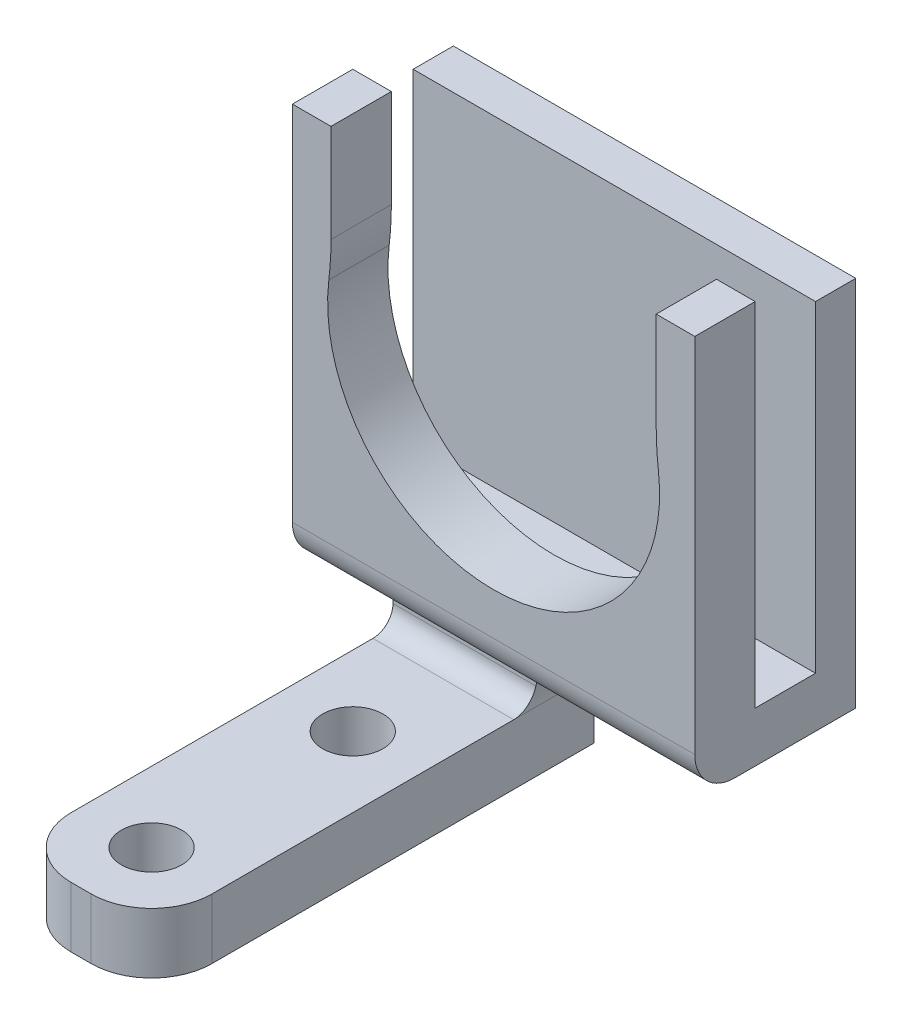
SolidWorks part; units mm, degrees
ref_plane "Front Plane" through (0, 0, 0) normal (0, 0, 1) x (1, 0, 0)
ref_plane "Top Plane" through (0, 0, 0) normal (0, 1, 0) x (1, 0, 0)
ref_plane "Right Plane" through (0, 0, 0) normal (1, 0, 0) x (0, 0, -1)
sketch "Sketch1" plane through (0, 0, 0) normal (0, 0, 1) x (1, 0, 0)
  line L0 (18.0821, 20) -> (20, 20)
  line L1 (0, 0) -> (20, 0)
  line L2 (0, 0) -> (0, 20)
  line L3 (0, 20) -> (1.9179, 20)
  line L4 (20, 0) -> (20, 20)
  line L5 (1.9179, 20) -> (1.9179, 14)
  line L6 (18.0821, 20) -> (18.0821, 14)
  arc A1 (1.9179, 14) -> (18.0821, 14) centre (10, 12.3441) ccw
  dimension "D3" = 6
  dimension "D5" = 8.25
  dimension "D1" = 20
  dimension "D2" = 20
  dimension "D4" = 6
extrude "Boss-Extrude1" add sketch "Sketch1" along normal blind 3 contours L0 L4 L1 L2 L3 L5 A1 L6
sketch "Sketch2" plane through (0, 0, 0) normal (0, 0, -1) x (-1, 0, 0)
  line L0 (0, 0) -> (0, 20) construction
  line L1 (-20, 0) -> (0, 0)
  line L2 (-20, 0) -> (-20, 2.5)
  line L3 (-20, 2.5) -> (0, 2.5)
  line L4 (0, 0) -> (0, 2.5)
  dimension "D1" = 2.5
extrude "Boss-Extrude2" add sketch "Sketch2" along normal blind 5
sketch "Sketch3" plane through (0, 2.5, 0) normal (0, 1, 0) x (1, 0, 0)
  line L0 (0, 5) -> (0, 0) construction
  line L1 (20, 5) -> (0, 5)
  line L2 (20, 5) -> (20, 3)
  line L3 (20, 3) -> (0, 3)
  line L4 (0, 5) -> (0, 3)
  dimension "D1" = 2
extrude "Boss-Extrude3" add sketch "Sketch3" along normal blind 16
fillet "Fillet1" radius 15 2 edges at (18.0821, 14, 1.5) (1.9179, 14, 1.5)
sketch "Sketch4" plane through (0, 0, 0) normal (0, -1, 0) x (1, 0, 0)
  line L1 (7, -5) -> (0, -5)
  line L2 (7, -5) -> (7, 3)
  line L3 (7, 3) -> (0, 3)
  line L4 (0, -5) -> (0, 3)
  dimension "D1" = 7
extrude "Boss-Extrude4" add sketch "Sketch4" along normal blind 5
sketch "Sketch5" plane through (0, 0, -5) normal (0, 0, -1) x (-1, 0, 0)
  line L4 (-7, -8) -> (0, -8)
  line L5 (-7, -5) -> (0, -5)
  line L6 (-7, -5) -> (-7, -8)
  line L7 (-7, -5) -> (-7, 0) construction
  line L9 (0, -5) -> (0, -8)
  line L10 (0, -5) -> (0, 18.5) construction
  dimension "D1" = 3
extrude "Boss-Extrude5" add sketch "Sketch5" against normal blind 22 contours L5 L9 L4 L6
fillet "Fillet2" radius 5 1 edges at (7, 0, -1)
sketch "Sketch6" plane through (0, -8, 0) normal (0, -1, 0) x (-1, 0, 0)
  line L1 (-3.5, -17) -> (-3.5, 5)
  line L2 (-7, 5) -> (0, 5) construction
  line L3 (-7, -17) -> (0, -17) construction
  circle A0 centre (-3.5, -13.5) radius 1.5
  circle A1 centre (-3.5, -3.5) radius 1.5
  point P10 (0, 0)
  point P11 (0, 0)
  dimension "D1" = 3
  dimension "D2" = 3
  dimension "D3" = 3.5
  dimension "D4" = 10
sketch "Sketch7" plane through (0, 0, 0) normal (-1, 0, 0) x (0, 0, 1)
  line L1 (-2, 0) -> (3, 0)
  line L2 (-2, 0) -> (-2, -5)
  line L4 (3, 0) -> (3, -5)
  line L6 (-3, 2.5) -> (0, 2.5) construction
  line L7 (3, -5) -> (3, 20) construction
  line L8 (-2, -5) -> (3, -5)
  line L9 (-5, -8) -> (-5, 18.5) construction
  line L10 (17, -5) -> (3, -5) construction
  dimension "D1" = 2.5
  dimension "D2" = 0
  dimension "D3" = 3
extrude "Cut-Extrude1" cut sketch "Sketch7" against normal through all
fillet "Fillet3" radius 2 2 edges at (6, 0, -2) (10, 0, 3)
extrude "Cut-Extrude2" cut sketch "Sketch6" against normal blind 5 contours L1 A1 | L1 A1 | L1 A0 | L1 A0 region at (4.1366, -8, 13.5) region at (4.1366, -8, 3.5) region at (2.8634, -8, 3.5) region at (2.8634, -8, 13.5)
fillet "Fillet4" radius 3 2 edges at (7, -6.5, 17) (0, -6.5, 17)
fillet "Fillet5" radius 1 1 edges at (3.5, -5, -2)
